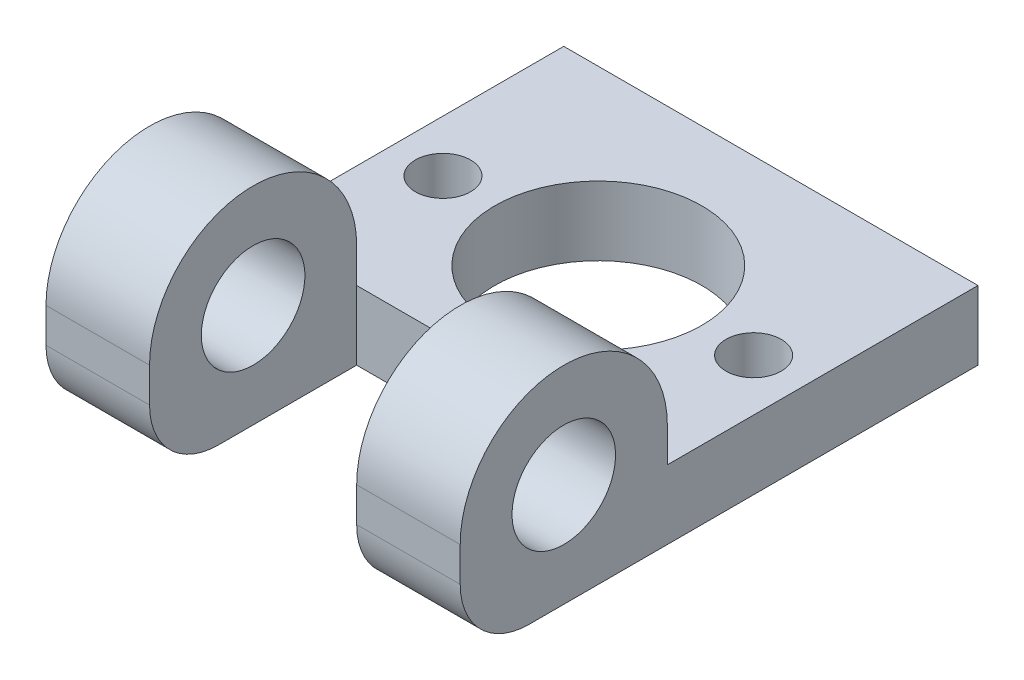
SolidWorks part; units mm, degrees
ref_plane "前视基准面" through (0, 0, 0) normal (0, 0, 1) x (1, 0, 0)
ref_plane "上视基准面" through (0, 0, 0) normal (0, 1, 0) x (1, 0, 0)
ref_plane "右视基准面" through (0, 0, 0) normal (1, 0, 0) x (0, 0, -1)
sketch "草图1" plane through (0, 0, 0) normal (0, 1, 0) x (1, 0, 0)
  line L0 (-4.5, 2.5) -> (4.5, 2.5) construction
  line L1 (6, -7.5) -> (-6, -7.5)
  line L2 (6, -7.5) -> (6, 7.5)
  line L3 (6, 7.5) -> (-6, 7.5)
  line L4 (-6, -7.5) -> (-6, 7.5)
  line L5 (0, 7.5) -> (0, -7.5) construction
  line L6 (6, 0) -> (-6, 0) construction
  line L7 (0, 2.5) -> (0, 7.5) construction
  circle A0 centre (-4.5, 2.5) radius 0.8
  circle A1 centre (4.5, 2.5) radius 0.8
  circle A2 centre (0, 2.5) radius 3
  point P0 (0, 0)
  dimension "D3" = 9
  dimension "D4" = 1.6
  dimension "D5" = 5
  dimension "D6" = 6
  dimension "D1" = 12
  dimension "D2" = 15
extrude "凸台-拉伸1" add sketch "草图1" along normal blind 2
sketch "草图2" plane through (-6, 0, 0) normal (-1, 0, 0) x (0, 0, 1)
  line L1 (1.5, 3) -> (1.5, 2)
  line L2 (-7.5, 2) -> (7.5, 2) construction
  line L3 (7.5, 2) -> (7.5, 3)
  line L4 (-7.5, 0) -> (7.5, 0) construction
  arc A0 (7.5, 3) -> (1.5, 3) centre (4.5, 3) ccw
  circle A1 centre (4.5, 3) radius 1.5
  line M3 (7.5, 2) -> (-7.5, 2)
  dimension "D1" = 1.5
  dimension "D2" = 3
  dimension "D3" = 3
extrude "凸台-拉伸3" add sketch "草图2" against normal up to surface (12 mm away) contours A1 A0 M3 region at (-6, 5.9279, 4.5) up to face at (6, 1, 0)
extrude "切除-拉伸1" cut sketch "草图2<3>" against normal up to next contours A1
sketch "草图2<3>" plane through (-6, 0, 0) normal (-1, 0, 0) x (0, 0, 1) same geometry as "草图2"
ref_plane "基准面1" through (0, 0, 0) normal (-1, 0, 0) x (0, 0, 1)
sketch "草图5" plane through (0, 0, 0) normal (-1, 0, 0) x (0, 0, 1)
  line L0 (1.5, 2) -> (1.5, 0)
  line L4 (-7.5, 0) -> (7.5, 0)
  line L5 (-7.5, 2) -> (-7.5, 0)
  line L6 (1.5, 2) -> (-7.5, 2)
  line L7 (7.5, 0) -> (7.5, 3)
  line L8 (1.5, 0) -> (7.5, 0)
  line L11 (7.5, 0) -> (7.5, 3)
  line L12 (1.5, 3) -> (1.5, 2)
  line L13 (1.5, 3) -> (1.5, 2)
  arc A1 (7.5, 3) -> (1.5, 3) centre (4.5, 3) ccw
  arc A2 (7.5, 3) -> (1.5, 3) centre (4.5, 3) ccw
  dimension "D1" = 0
extrude "切除-拉伸2" cut sketch "草图5" against normal blind 3 and the other way blind 3
fillet "圆角1" radius 2 1 edges at (-4.5, 0, 7.5)
